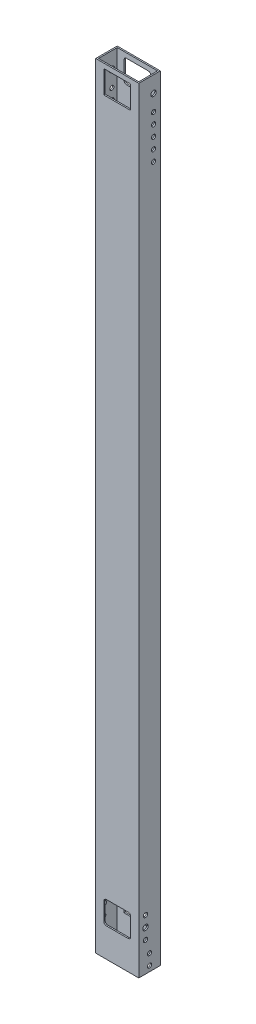
SolidWorks part; units mm, degrees
material "6061-T6 (SS)"
ref_plane "Front Plane" through (0, 0, 0) normal (0, 0, 1) x (1, 0, 0)
ref_plane "Top Plane" through (0, 0, 0) normal (0, 1, 0) x (1, 0, 0)
ref_plane "Right Plane" through (0, 0, 0) normal (1, 0, 0) x (0, 0, -1)
sketch "Sketch1" plane through (0, 0, 0) normal (0, 0, 1) x (1, 0, 0)
  line L1 (-25.4, -457.2) -> (25.4, -457.2)
  line L2 (-25.4, -457.2) -> (-25.4, 457.2)
  line L3 (-25.4, 457.2) -> (25.4, 457.2)
  line L4 (25.4, -457.2) -> (25.4, 457.2)
  line L5 (-25.4, -457.2) -> (25.4, 457.2) construction
  line L6 (-25.4, 457.2) -> (25.4, -457.2) construction
  point P0 (0, 0)
  dimension "D1" = 50.8
  dimension "D2" = 914.4
extrude "Boss-Extrude1" add sketch "Sketch1" along normal mid plane 25.4
shell "Shell1" thickness 1.5875 removed face at (0, -457.2, 0) removed face at (0, 457.2, 0)
sketch "Sketch3" plane through (0, 0, 0) normal (1, 0, 0) x (0, 0, -1)
  line L0 (-12.7, -457.2) -> (12.7, -457.2) construction
  circle A0 centre (0, -450.85) radius 2.4892
  circle A1 centre (0, -438.15) radius 2.4892
  point P6 (0, -457.2)
  dimension "D1" = 4.9784
  dimension "D2" = 6.35
  dimension "D3" = 12.7
extrude "Cut-Extrude1" cut sketch "Sketch3" against normal through all both and the other way through all
sketch "Sketch4" plane through (0, 0, 0) normal (1, 0, 0) x (0, 0, -1)
  line L4 (-12.7, -457.2) -> (12.7, -457.2) construction
  line L5 (-12.7, 457.2) -> (-12.7, -457.2) construction
  circle A3 centre (-4.7625, -409.575) radius 3.175
  circle A4 centre (-4.7625, -396.875) radius 2.4892
  circle A5 centre (-4.7625, -422.275) radius 2.4892
  dimension "D7" = 6.35
  dimension "D8" = 4.9784
  dimension "D9" = 12.7
  dimension "D10" = 12.7
  dimension "D11" = 47.625
  dimension "D12" = 7.9375
extrude "Cut-Extrude2" cut sketch "Sketch4" against normal through all both and the other way through all
sketch "Sketch5" plane through (0, 0, 0) normal (0, 0, 1) x (1, 0, 0)
  line L0 (-25.4, -457.2) -> (25.4, -457.2) construction
  line L1 (-15.875, -396.0813) -> (15.875, -396.0813)
  line L2 (-15.875, -396.0813) -> (-15.875, -423.0688)
  line L3 (-15.875, -423.0688) -> (15.875, -423.0688)
  line L4 (15.875, -396.0813) -> (15.875, -423.0688)
  point P4 (0, -423.0688)
  point P7 (0, -457.2)
  point P8 (15.875, -409.575)
  dimension "D1" = 31.75
  dimension "D2" = 26.9875
  dimension "D3" = 47.625
extrude "Cut-Extrude3" cut sketch "Sketch5" along normal through all both and the other way through all
fillet "Fillet1" radius 3.175 4 edges at (-15.875, -423.0688, 11.9062) (15.875, -423.0688, 11.9062) (-15.875, -396.0813, 11.9062) (15.875, -396.0813, 11.9062)
sketch "Sketch6" plane through (0, 0, 0) normal (1, 0, 0) x (0, 0, -1)
  line L0 (12.7, 457.2) -> (12.7, -457.2) construction
  line L1 (-12.7, 457.2) -> (12.7, 457.2) construction
  circle A0 centre (4.7625, 438.15) radius 3.175
  dimension "D1" = 6.35
  dimension "D2" = 7.9375
  dimension "D3" = 19.05
extrude "Cut-Extrude4" cut sketch "Sketch6" against normal through all both and the other way through all
sketch "Sketch7" plane through (0, 0, 0) normal (0, 0, 1) x (1, 0, 0)
  line L0 (25.4, 457.2) -> (-25.4, 457.2) construction
  line L1 (15.875, 451.6437) -> (-15.875, 451.6437)
  line L2 (15.875, 451.6437) -> (15.875, 424.6562)
  line L3 (15.875, 424.6562) -> (-15.875, 424.6563)
  line L4 (-15.875, 451.6437) -> (-15.875, 424.6563)
  point P5 (0, 451.6438)
  point P8 (0, 457.2)
  point P9 (-15.875, 438.15)
  dimension "D1" = 26.9875
  dimension "D2" = 31.75
  dimension "D3" = 19.05
extrude "Cut-Extrude5" cut sketch "Sketch7" against normal through all both and the other way through all
fillet "Fillet2" radius 3.175 4 edges at (15.875, 424.6562, -11.9062) (-15.875, 424.6563, -11.9062) (-15.875, 451.6437, -11.9062) (15.875, 451.6437, -11.9062)
sketch "Sketch8" plane through (0, 0, 0) normal (1, 0, 0) x (0, 0, -1)
  line L0 (12.7, 457.2) -> (12.7, -457.2) construction
  line L1 (-12.7, 457.2) -> (12.7, 457.2) construction
  circle A0 centre (4.7625, 419.1) radius 2.4892
  circle A1 centre (4.7625, 406.4) radius 2.4892
  circle A2 centre (4.7625, 393.7) radius 2.4892
  circle A3 centre (4.7625, 381) radius 2.4892
  circle A4 centre (4.7625, 368.3) radius 2.4892
  dimension "D3" = 4.9784
  dimension "D1" = 7.9375
  dimension "D2" = 38.1
  dimension "D5" = 12.7
  dimension "D4" = 5
extrude "Cut-Extrude6" cut sketch "Sketch8" against normal through all both and the other way through all
